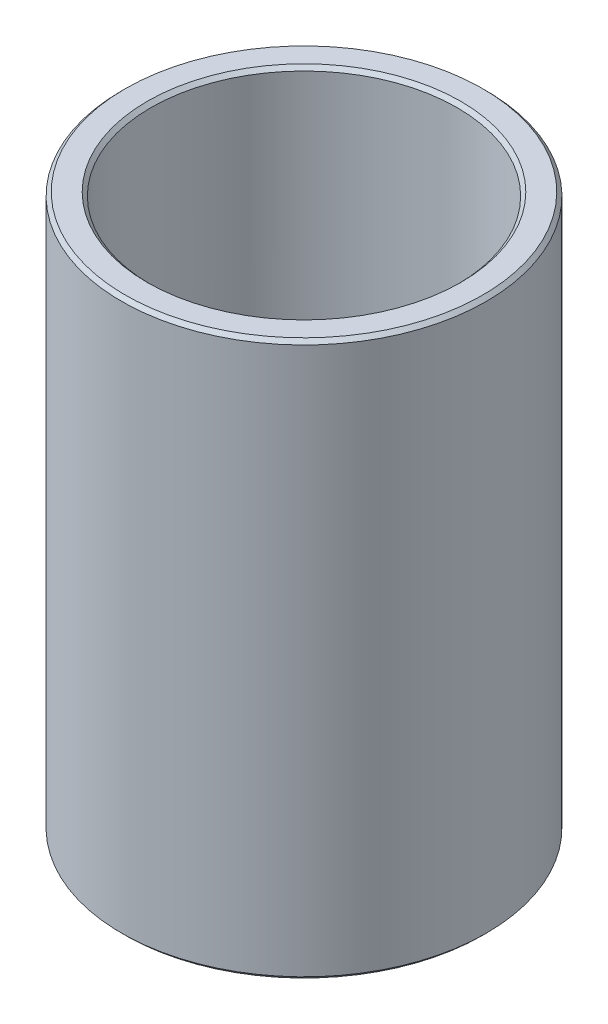
SolidWorks part; units mm, degrees
material "Brass"
ref_plane "Front Plane" through (0, 0, 0) normal (0, 0, 1) x (1, 0, 0)
ref_plane "Top Plane" through (0, 0, 0) normal (0, 1, 0) x (1, 0, 0)
ref_plane "Right Plane" through (0, 0, 0) normal (1, 0, 0) x (0, 0, -1)
sketch "Sketch1" plane through (0, 0, 0) normal (0, 0, 1) x (1, 0, 0)
  line L0 (0, -587.1511) -> (0, 28770.4063) construction
  line L1 (2, 0) -> (2, 1)
  line L2 (2, 1) -> (5, 4)
  line L3 (5, 4) -> (10.5, 4)
  line L4 (10.5, 4) -> (10.5, 38)
  line L5 (10.5, 38) -> (12.5, 38)
  line L6 (12.5, 38) -> (12.5, 0)
  line L7 (12.5, 0) -> (2, 0)
  point P5 (2.6696, 3.6507)
  point P11 (4.4824, 5.5519)
  point P12 (0, 0)
  dimension "D1" = 25
  dimension "D2" = 38
  dimension "D3" = 2
  dimension "D4" = 4
  dimension "D5" = 4
  dimension "D6" = 45
  dimension "D7" = 10
revolve "Revolve1" add sketch "Sketch1" angle 360 about L0
chamfer "Chamfer1" distance 0.25 angle 45 4 edges at (12.5, 38, 0) (10.5, 38, 0) (12.5, 0, 0) (2, 0, 0)
